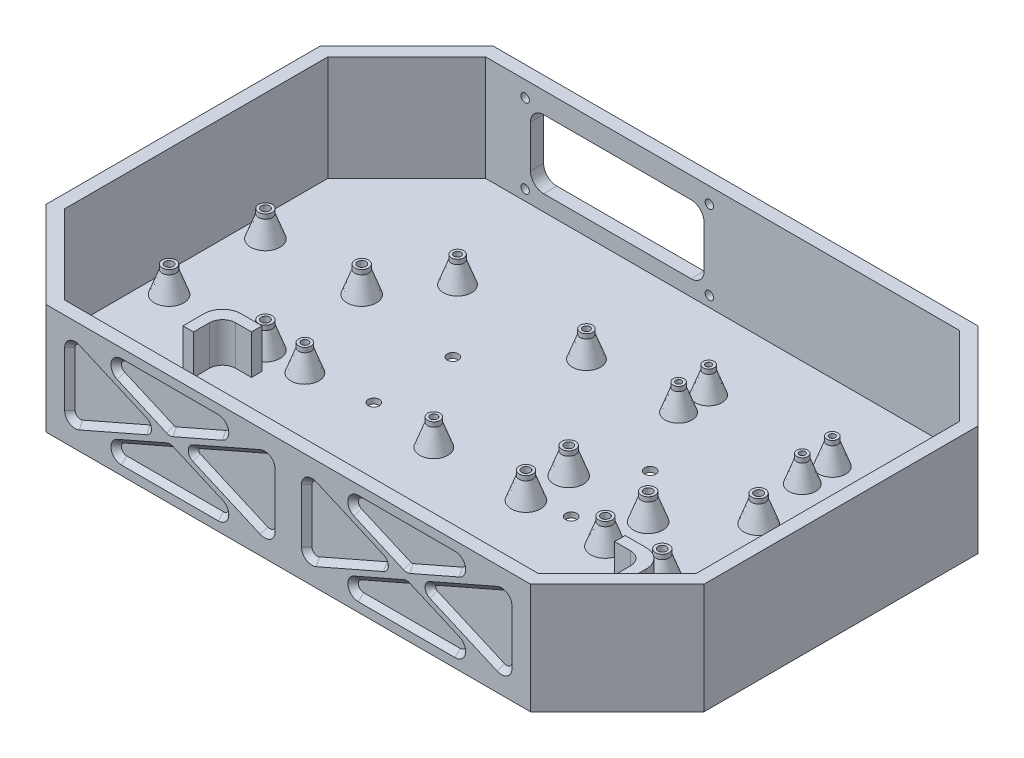
SolidWorks part; units mm, degrees
note: '?' marks a value the reader was unsure of. The reader was unsure of these and kept them because the rebuilt part matched: shared geometry of "Sketch1<3>", "Sketch2<3>", "Sketch4<3>".
ref_plane "Front Plane" through (0, 0, 0) normal (0, 0, 1) x (1, 0, 0)
ref_plane "Top Plane" through (0, 0, 0) normal (0, 1, 0) x (1, 0, 0)
ref_plane "Right Plane" through (0, 0, 0) normal (1, 0, 0) x (0, 0, -1)
ref_axis "X" through (-88.99, 0, 0) along (1, 0, 0)?
ref_axis "Y" through (0, 55, 0) along (0, -1, 0)?
ref_axis "Z" through (0, 0, -88.99) along (0, 0, 1)?
sketch "Sketch1" plane through (0, 0, 0) normal (0, 1, 0) x (1, 0, 0)
  line L0 (90, 80) -> (120, 50)
  line L1 (-90, 80) -> (90, 80)
  line L2 (-90, 80) -> (-90, -80) construction
  line L3 (-90, -80) -> (90, -80)
  line L4 (90, 80) -> (90, -80) construction
  line L5 (-90, 80) -> (90, -80) construction
  line L6 (-90, -80) -> (90, 80) construction
  line L7 (120, 50) -> (120, -50)
  line L8 (120, -50) -> (90, -80)
  line L9 (90, 0) -> (120, 0) construction
  line L10 (0, 0) -> (0, 80) construction
  line L11 (-120, -50) -> (-90, -80)
  line L12 (-120, 50) -> (-120, -50)
  line L13 (-90, 80) -> (-120, 50)
  line L14 (125, 52.0711) -> (125, -52.0711)
  line L15 (125, -52.0711) -> (92.0711, -85)
  line L16 (-92.0711, -85) -> (92.0711, -85)
  line L17 (-125, -52.0711) -> (-92.0711, -85)
  line L18 (-125, 52.0711) -> (-125, -52.0711)
  line L19 (-92.0711, 85) -> (-125, 52.0711)
  line L20 (-92.0711, 85) -> (92.0711, 85)
  line L21 (92.0711, 85) -> (125, 52.0711)
  point P0 (0, 0)
  dimension "D1" = 160
  dimension "D2" = 180
  dimension "D3" = 100
  dimension "D4" = 45
  dimension "D5" = 5
extrude "Boss-Extrude1" add sketch "Sketch1" against normal blind 2 contours L18 L17 L16 L15 L14 L21 L20 L19
extrude "Boss-Extrude2" add sketch "Sketch1<3>" along normal blind 40 contours L21 L20 L19 L18 L17 L16 L15 L14 L13 L1 L0 L7 L8 L3 L11 L12
sketch "Sketch1<3>" plane through (0, 0, 0) normal (0, 1, 0) x (1, 0, 0) same geometry as "Sketch1"
sketch "Sketch2" plane through (0, 0, 0) normal (0, 1, 0) x (1, 0, 0)
  line L0 (93.7, 0) -> (0, 0) construction
  line L1 (-112, 18.3) -> (-75.4, 18.3) construction
  line L2 (-112, 18.3) -> (-112, -18.3) construction
  line L3 (-112, -18.3) -> (-75.4, -18.3) construction
  line L4 (-75.4, 18.3) -> (-75.4, -18.3) construction
  line L5 (-112, 18.3) -> (-75.4, -18.3) construction
  line L6 (-112, -18.3) -> (-75.4, 18.3) construction
  line L7 (75.4, 18.3) -> (112, 18.3) construction
  line L8 (75.4, 18.3) -> (75.4, -18.3) construction
  line L9 (75.4, -18.3) -> (112, -18.3) construction
  line L10 (112, 18.3) -> (112, -18.3) construction
  line L11 (75.4, 18.3) -> (112, -18.3) construction
  line L12 (75.4, -18.3) -> (112, 18.3) construction
  line L13 (23.6, -2.05) -> (53.8, -2.05) construction
  line L14 (23.6, -2.05) -> (23.6, -18.3) construction
  line L15 (23.6, -18.3) -> (53.8, -18.3) construction
  line L16 (53.8, -2.05) -> (53.8, -18.3) construction
  line L17 (23.6, -2.05) -> (53.8, -18.3) construction
  line L18 (23.6, -18.3) -> (53.8, -2.05) construction
  line L19 (23.6, 51.1) -> (70.6, 51.1) construction
  line L20 (23.6, 51.1) -> (23.6, 39.7) construction
  line L21 (23.6, 39.7) -> (70.6, 39.7) construction
  line L22 (70.6, 51.1) -> (70.6, 39.7) construction
  line L23 (23.6, 51.1) -> (70.6, 39.7) construction
  line L24 (23.6, 39.7) -> (70.6, 51.1) construction
  line L25 (-60.4, 39.7) -> (-11.4, 39.7) construction
  line L26 (-60.4, 39.7) -> (-60.4, -18.3) construction
  line L27 (-60.4, -18.3) -> (-11.4, -18.3) construction
  line L28 (-11.4, 39.7) -> (-11.4, -18.3) construction
  line L29 (-60.4, 39.7) -> (-11.4, -18.3) construction
  line L30 (-60.4, -18.3) -> (-11.4, 39.7) construction
  line L31 (0, 0) -> (-93.7, 0) construction
  line L32 (120, 50) -> (120, -50) construction
  circle A0 centre (112, -18.3) radius 1.6
  circle A1 centre (75.4, -18.3) radius 1.6
  circle A2 centre (75.4, 18.3) radius 1.6
  circle A3 centre (112, 18.3) radius 1.6
  circle A4 centre (-75.4, 18.3) radius 1.6
  circle A5 centre (-75.4, -18.3) radius 1.6
  circle A6 centre (-112, -18.3) radius 1.6
  circle A7 centre (-112, 18.3) radius 1.6
  circle A8 centre (53.8, -18.3) radius 1.6
  circle A9 centre (23.6, -18.3) radius 1.6
  circle A10 centre (23.6, -2.05) radius 1.6
  circle A11 centre (53.8, -2.05) radius 1.6
  circle A12 centre (70.6, 39.7) radius 1.1
  circle A13 centre (23.6, 39.7) radius 1.1
  circle A14 centre (23.6, 51.1) radius 1.1
  circle A15 centre (70.6, 51.1) radius 1.1
  circle A16 centre (-11.4, 39.7) radius 1.35
  circle A17 centre (-60.4, 39.7) radius 1.35
  circle A18 centre (-60.4, -18.3) radius 1.35
  circle A19 centre (-11.4, -18.3) radius 1.35
  circle A20 centre (-112, 18.3) radius 2.6
  circle A21 centre (-112, -18.3) radius 2.6
  circle A22 centre (-75.4, -18.3) radius 2.6
  circle A23 centre (-75.4, 18.3) radius 2.6
  circle A24 centre (-60.4, 39.7) radius 2.35
  circle A25 centre (-11.4, 39.7) radius 2.35
  circle A26 centre (-11.4, -18.3) radius 2.35
  circle A27 centre (-60.4, -18.3) radius 2.35
  circle A28 centre (23.6, -18.3) radius 2.6
  circle A29 centre (23.6, -2.05) radius 2.6
  circle A30 centre (53.8, -2.05) radius 2.6
  circle A31 centre (53.8, -18.3) radius 2.6
  circle A32 centre (23.6, 51.1) radius 2.1
  circle A33 centre (23.6, 39.7) radius 2.1
  circle A34 centre (70.6, 39.7) radius 2.1
  circle A35 centre (70.6, 51.1) radius 2.1
  circle A36 centre (75.4, 18.3) radius 2.6
  circle A37 centre (112, 18.3) radius 2.6
  circle A38 centre (112, -18.3) radius 2.6
  circle A39 centre (75.4, -18.3) radius 2.6
  point P0 (-93.7, 0)
  point P5 (93.7, 0)
  point P10 (38.7, -10.175)
  point P16 (47.1, 45.4)
  point P21 (-35.9, 10.7)
  dimension "D9" = 3.2
  dimension "D10" = 3.2
  dimension "D11" = 2.2
  dimension "D12" = 2.7
  dimension "D1" = 36.6
  dimension "D2" = 49
  dimension "D3" = 58
  dimension "D4" = 11.4
  dimension "D5" = 47
  dimension "D6" = 16.25
  dimension "D7" = 30.2
  dimension "D8" = 35
  dimension "D13" = 8
  dimension "D14" = 15
  dimension "D15" = 1
extrude "Boss-Extrude3" add sketch "Sketch2" along normal blind 10 contours A20 | A21 | A22 | A23 | A24 | A27 | A26 | A25 | A33 | A32 | A34 | A35 | A30 | A29 | A28 | A31 | A39 | A36 | A37 | A38
extrude "Cut-Extrude1" cut sketch "Sketch2<3>" against normal through all both and the other way through all contours A6 | A7 | A4 | A5 | A18 | A17 | A19 | A16 | A13 | A14 | A15 | A12 | A2 | A11 | A10 | A9 | A8 | A1 | A3 | A0
sketch "Sketch2<3>" plane through (0, 0, 0) normal (0, 1, 0) x (1, 0, 0) same geometry as "Sketch2"
sketch "Sketch3" plane through (0, 0, 0) normal (0, 1, 0) x (1, 0, 0)
  line L0 (0, -55) -> (0, 0) construction
  line L1 (-80, -30) -> (80, -30)
  line L2 (-80, -30) -> (-80, -80)
  line L3 (-80, -80) -> (80, -80)
  line L4 (80, -30) -> (80, -80)
  line L5 (-80, -30) -> (80, -80) construction
  line L6 (-80, -80) -> (80, -30) construction
  line L8 (-80, -41) -> (-84, -41)
  line L9 (-84, -41) -> (-84, -26)
  line L10 (-84, -26) -> (-69, -26)
  line L11 (-69, -26) -> (-69, -30)
  line L12 (69, -30) -> (69, -26)
  line L13 (69, -26) -> (84, -26)
  line L14 (84, -26) -> (84, -41)
  line L15 (84, -41) -> (80, -41)
  line L16 (-90, -80) -> (90, -80) construction
  point P0 (0, -55)
  dimension "D2" = 15
  dimension "D3" = 4
  dimension "D4" = 50
  dimension "D5" = 160
extrude "Boss-Extrude4" add sketch "Sketch3" along normal blind 15 contours L11 L10 L9 L8 L2 L1 | L15 L14 L13 L12 L1 L4
fillet "Fillet1" radius 5 2 edges at (80, 7.5, 30) (-80, 7.5, 30)
fillet "Fillet2" radius 7 2 edges at (84, 7.5, 26) (-84, 7.5, 26)
sketch "Sketch4" plane through (0, 0, 0) normal (0, 0, 1) x (1, 0, 0)
  line L0 (0, -2) -> (0, 40) construction
  line L1 (-92.0711, -2) -> (92.0711, -2) construction
  line L2 (-92.0711, 40) -> (92.0711, 40) construction
  line L3 (0, 19) -> (-40, 19) construction
  line L4 (0, 19) -> (45, 19) construction
  line L5 (54.5788, 19.9162) -> (80.1984, 31.1247)
  line L6 (-75, 34) -> (-5, 34) construction
  line L7 (-75, 34) -> (-75, 4) construction
  line L8 (-75, 4) -> (-5, 4) construction
  line L9 (-5, 34) -> (-5, 4) construction
  line L10 (-75, 34) -> (-5, 4) construction
  line L11 (-75, 4) -> (-5, 34) construction
  line L12 (5, 36.5) -> (85, 36.5) construction
  line L13 (5, 36.5) -> (5, 1.5) construction
  line L14 (5, 1.5) -> (85, 1.5) construction
  line L15 (85, 36.5) -> (85, 1.5) construction
  line L16 (5, 36.5) -> (85, 1.5) construction
  line L17 (5, 1.5) -> (85, 36.5) construction
  line L18 (83, 29.2924) -> (83, 8.7076)
  line L19 (80.1984, 6.8753) -> (54.5788, 18.0838)
  line L20 (53.9796, 19) -> (45, 19) construction
  line L21 (64.1843, 30.6677) -> (45.4008, 22.4499)
  line L22 (44.5992, 22.4499) -> (25.8157, 30.6677)
  line L23 (26.6173, 34.5) -> (63.3827, 34.5)
  line L24 (45, 19) -> (45, 22.3661) construction
  line L25 (26.6173, 3.5) -> (63.3827, 3.5)
  line L26 (44.5992, 15.5501) -> (25.8157, 7.3323)
  line L27 (64.1843, 7.3323) -> (45.4008, 15.5501)
  line L28 (9.8016, 6.8753) -> (35.4212, 18.0838)
  line L29 (7, 29.2924) -> (7, 8.7076)
  line L30 (35.4212, 19.9162) -> (9.8016, 31.1247)
  line L31 (-73, 27) -> (-73, 11)
  line L32 (-68, 6) -> (-12, 6)
  line L33 (-7, 27) -> (-7, 11)
  line L34 (-68, 32) -> (-12, 32)
  line L35 (-73, 32) -> (-7, 32) construction
  line L36 (-7, 32) -> (-7, 6) construction
  line L37 (-73, 6) -> (-7, 6) construction
  line L38 (-73, 32) -> (-73, 6) construction
  arc A0 (80.1984, 31.1247) -> (83, 29.2924) centre (81, 29.2924) cw
  arc A1 (83, 8.7076) -> (80.1984, 6.8753) centre (81, 8.7076) cw
  arc A2 (54.5788, 18.0838) -> (54.5788, 19.9162) centre (54.9796, 19) cw
  arc A3 (45.4008, 22.4499) -> (44.5992, 22.4499) centre (45, 23.3661) cw
  arc A4 (25.8157, 30.6677) -> (26.6173, 34.5) centre (26.6173, 32.5) cw
  arc A5 (63.3827, 34.5) -> (64.1843, 30.6677) centre (63.3827, 32.5) cw
  arc A6 (63.3827, 3.5) -> (64.1843, 7.3323) centre (63.3827, 5.5) ccw
  arc A7 (25.8157, 7.3323) -> (26.6173, 3.5) centre (26.6173, 5.5) ccw
  arc A8 (45.4008, 15.5501) -> (44.5992, 15.5501) centre (45, 14.6339) ccw
  arc A9 (35.4212, 18.0838) -> (35.4212, 19.9162) centre (35.0204, 19) ccw
  arc A10 (7, 8.7076) -> (9.8016, 6.8753) centre (9, 8.7076) ccw
  arc A11 (9.8016, 31.1247) -> (7, 29.2924) centre (9, 29.2924) ccw
  arc A12 (-12, 32) -> (-7, 27) centre (-12, 27) cw
  arc A13 (-7, 11) -> (-12, 6) centre (-12, 11) cw
  arc A14 (-73, 11) -> (-68, 6) centre (-68, 11) ccw
  arc A15 (-73, 27) -> (-68, 32) centre (-68, 27) cw
  circle A16 centre (-75, 34) radius 1.6
  circle A17 centre (-5, 34) radius 1.6
  circle A18 centre (-5, 4) radius 1.6
  circle A19 centre (-75, 4) radius 1.6
  point P76 (-75, 3.5046)
  dimension "D4" = 3
  dimension "D5" = 1
  dimension "D6" = 2
  dimension "D8" = 3
  dimension "D13" = 5
  dimension "D14" = 3.2
  dimension "D1" = 30
  dimension "D2" = 70
  dimension "D3" = 40
  dimension "D7" = 2
  dimension "D9" = 2
  dimension "D10" = 80
  dimension "D11" = 35
  dimension "D15" = 45
  dimension "D12" = 2
extrude "Cut-Extrude2" cut sketch "Sketch4" along normal up to surface (5 mm away) from surface at -85 contours A15 L31 A14 L32 A13 L33 A12 L34 | A16 | A19 | A18 | A17 up to face at (0, 20, -80) starting at face at (0, 19, -85)
extrude "Cut-Extrude3" cut sketch "Sketch4<3>" along normal blind 2 from surface at -85 contours L30 A11 L29 A10 L28 A9 | A5 L23 A4 L22 A3 L21 | L27 A8 L26 A7 L25 A6 | A2 L19 A1 L18 A0 L5 starting at face at (0, 19, -85)
sketch "Sketch4<3>" plane through (0, 0, 0) normal (0, 0, 1) x (1, 0, 0) same geometry as "Sketch4"
sketch "Sketch5" plane through (0, 0, 0) normal (0, 0, 1) x (1, 0, 0)
  line L0 (44.5992, 15.5501) -> (25.8157, 7.3323) construction
  line L1 (64.1843, 7.3323) -> (45.4008, 15.5501) construction
  line L2 (26.6173, 3.5) -> (63.3827, 3.5) construction
  line L3 (83, 29.2924) -> (83, 8.7076) construction
  line L4 (54.5788, 19.9162) -> (80.1984, 31.1247) construction
  line L5 (80.1984, 6.8753) -> (54.5788, 18.0838) construction
  line L6 (64.1843, 30.6677) -> (45.4008, 22.4499) construction
  line L7 (26.6173, 34.5) -> (63.3827, 34.5) construction
  line L8 (44.5992, 22.4499) -> (25.8157, 30.6677) construction
  line L9 (9.8016, 6.8753) -> (35.4212, 18.0838) construction
  line L10 (7, 29.2924) -> (7, 8.7076) construction
  line L11 (35.4212, 19.9162) -> (9.8016, 31.1247) construction
  line L12 (44.5992, 15.5501) -> (25.8157, 7.3323)
  line L13 (64.1843, 7.3323) -> (45.4008, 15.5501)
  line L14 (26.6173, 3.5) -> (63.3827, 3.5)
  line L15 (83, 29.2924) -> (83, 8.7076)
  line L16 (54.5788, 19.9162) -> (80.1984, 31.1247)
  line L17 (80.1984, 6.8753) -> (54.5788, 18.0838)
  line L18 (64.1843, 30.6677) -> (45.4008, 22.4499)
  line L19 (26.6173, 34.5) -> (63.3827, 34.5)
  line L20 (44.5992, 22.4499) -> (25.8157, 30.6677)
  line L21 (9.8016, 6.8753) -> (35.4212, 18.0838)
  line L22 (7, 29.2924) -> (7, 8.7076)
  line L23 (35.4212, 19.9162) -> (9.8016, 31.1247)
  line L24 (0, -2) -> (0, 40) construction
  line L25 (0, -2) -> (0, 40) construction
  line L26 (-35.4212, 19.9162) -> (-9.8016, 31.1247)
  line L27 (-7, 29.2924) -> (-7, 8.7076)
  line L28 (-9.8016, 6.8753) -> (-35.4212, 18.0838)
  line L29 (-44.5992, 22.4499) -> (-25.8157, 30.6677)
  line L30 (-26.6173, 34.5) -> (-63.3827, 34.5)
  line L31 (-64.1843, 30.6677) -> (-45.4008, 22.4499)
  line L32 (-80.1984, 6.8753) -> (-54.5788, 18.0838)
  line L33 (-54.5788, 19.9162) -> (-80.1984, 31.1247)
  line L34 (-83, 29.2924) -> (-83, 8.7076)
  line L35 (-26.6173, 3.5) -> (-63.3827, 3.5)
  line L36 (-64.1843, 7.3323) -> (-45.4008, 15.5501)
  line L37 (-44.5992, 15.5501) -> (-25.8157, 7.3323)
  arc A0 (25.8157, 7.3323) -> (26.6173, 3.5) centre (26.6173, 5.5) ccw construction
  arc A1 (45.4008, 15.5501) -> (44.5992, 15.5501) centre (45, 14.6339) ccw construction
  arc A2 (63.3827, 3.5) -> (64.1843, 7.3323) centre (63.3827, 5.5) ccw construction
  arc A3 (80.1984, 6.8753) -> (83, 8.7076) centre (81, 8.7076) ccw construction
  arc A4 (83, 29.2924) -> (80.1984, 31.1247) centre (81, 29.2924) ccw construction
  arc A5 (54.5788, 19.9162) -> (54.5788, 18.0838) centre (54.9796, 19) ccw construction
  arc A6 (44.5992, 22.4499) -> (45.4008, 22.4499) centre (45, 23.3661) ccw construction
  arc A7 (64.1843, 30.6677) -> (63.3827, 34.5) centre (63.3827, 32.5) ccw construction
  arc A8 (26.6173, 34.5) -> (25.8157, 30.6677) centre (26.6173, 32.5) ccw construction
  arc A9 (35.4212, 18.0838) -> (35.4212, 19.9162) centre (35.0204, 19) ccw construction
  arc A10 (7, 8.7076) -> (9.8016, 6.8753) centre (9, 8.7076) ccw construction
  arc A11 (9.8016, 31.1247) -> (7, 29.2924) centre (9, 29.2924) ccw construction
  arc A12 (25.8157, 7.3323) -> (26.6173, 3.5) centre (26.6173, 5.5) ccw
  arc A13 (45.4008, 15.5501) -> (44.5992, 15.5501) centre (45, 14.6339) ccw
  arc A14 (63.3827, 3.5) -> (64.1843, 7.3323) centre (63.3827, 5.5) ccw
  arc A15 (80.1984, 6.8753) -> (83, 8.7076) centre (81, 8.7076) ccw
  arc A16 (83, 29.2924) -> (80.1984, 31.1247) centre (81, 29.2924) ccw
  arc A17 (54.5788, 19.9162) -> (54.5788, 18.0838) centre (54.9796, 19) ccw
  arc A18 (44.5992, 22.4499) -> (45.4008, 22.4499) centre (45, 23.3661) ccw
  arc A19 (64.1843, 30.6677) -> (63.3827, 34.5) centre (63.3827, 32.5) ccw
  arc A20 (26.6173, 34.5) -> (25.8157, 30.6677) centre (26.6173, 32.5) ccw
  arc A21 (35.4212, 18.0838) -> (35.4212, 19.9162) centre (35.0204, 19) ccw
  arc A22 (7, 8.7076) -> (9.8016, 6.8753) centre (9, 8.7076) ccw
  arc A23 (9.8016, 31.1247) -> (7, 29.2924) centre (9, 29.2924) ccw
  arc A24 (-9.8016, 31.1247) -> (-7, 29.2924) centre (-9, 29.2924) cw
  arc A25 (-7, 8.7076) -> (-9.8016, 6.8753) centre (-9, 8.7076) cw
  arc A26 (-35.4212, 18.0838) -> (-35.4212, 19.9162) centre (-35.0204, 19) cw
  arc A27 (-26.6173, 34.5) -> (-25.8157, 30.6677) centre (-26.6173, 32.5) cw
  arc A28 (-64.1843, 30.6677) -> (-63.3827, 34.5) centre (-63.3827, 32.5) cw
  arc A29 (-44.5992, 22.4499) -> (-45.4008, 22.4499) centre (-45, 23.3661) cw
  arc A30 (-54.5788, 19.9162) -> (-54.5788, 18.0838) centre (-54.9796, 19) cw
  arc A31 (-83, 29.2924) -> (-80.1984, 31.1247) centre (-81, 29.2924) cw
  arc A32 (-80.1984, 6.8753) -> (-83, 8.7076) centre (-81, 8.7076) cw
  arc A33 (-63.3827, 3.5) -> (-64.1843, 7.3323) centre (-63.3827, 5.5) cw
  arc A34 (-45.4008, 15.5501) -> (-44.5992, 15.5501) centre (-45, 14.6339) cw
  arc A35 (-25.8157, 7.3323) -> (-26.6173, 3.5) centre (-26.6173, 5.5) cw
extrude "Cut-Extrude4" cut sketch "Sketch5" against normal blind 2 from surface at 85 starting at face at (0, 19, 85)
chamfer "Chamfer1" distance 2 angle 45 72 edges at (45, 15.6339, -85) (35.2074, 11.4412, -85) (54.7926, 11.4412, -85) (24.6597, 5.0905, -85) (65.3403, 5.0905, -85) (45, 3.5, -85) (45, 22.3661, -85) (35.2074, 26.5588, -85) (54.7926, 26.5588, -85) (24.6597, 32.9095, -85) (65.3403, 32.9095, -85) (45, 34.5, -85) (53.9796, 19, -85) (67.3886, 25.5204, -85) (67.3886, 12.4796, -85) (82.0947, 30.9662, -85) (82.0947, 7.0338, -85) (83, 19, -85) (36.0204, 19, -85) (22.6114, 25.5204, -85) (22.6114, 12.4796, -85) (7.9053, 30.9662, -85) (7.9053, 7.0338, -85) (7, 19, -85) (53.9796, 19, 85) (67.3886, 25.5204, 85) (67.3886, 12.4796, 85) (82.0947, 30.9662, 85) (82.0947, 7.0338, 85) (83, 19, 85) (45, 22.3661, 85) (35.2074, 26.5588, 85) (54.7926, 26.5588, 85) (24.6597, 32.9095, 85) (65.3403, 32.9095, 85) (45, 34.5, 85) (45, 15.6339, 85) (54.7926, 11.4412, 85) (35.2074, 11.4412, 85) (65.3403, 5.0905, 85) (24.6597, 5.0905, 85) (45, 3.5, 85) (36.0204, 19, 85) (22.6114, 12.4796, 85) (22.6114, 25.5204, 85) (7.9053, 7.0338, 85) (7.9053, 30.9662, 85) (7, 19, 85) (-36.0204, 19, 85) (-22.6114, 25.5204, 85) (-22.6114, 12.4796, 85) (-7.9053, 30.9662, 85) (-7.9053, 7.0338, 85) (-7, 19, 85) (-45, 15.6339, 85) (-35.2074, 11.4412, 85) (-54.7926, 11.4412, 85) (-24.6597, 5.0905, 85) (-65.3403, 5.0905, 85) (-45, 3.5, 85) (-45, 22.3661, 85) (-54.7926, 26.5588, 85) (-35.2074, 26.5588, 85) (-65.3403, 32.9095, 85) (-24.6597, 32.9095, 85) (-45, 34.5, 85) (-53.9796, 19, 85) (-67.3886, 12.4796, 85) (-67.3886, 25.5204, 85) (-82.0947, 7.0338, 85) (-82.0947, 30.9662, 85) (-83, 19, 85)
sketch "Sketch6" plane through (0, 0, 0) normal (0, 1, 0) x (1, 0, 0)
  line L1 (-37.5, 15) -> (37.5, 15) construction
  line L2 (-37.5, 15) -> (-37.5, -15) construction
  line L3 (-37.5, -15) -> (37.5, -15) construction
  line L4 (37.5, 15) -> (37.5, -15) construction
  line L5 (-37.5, 15) -> (37.5, -15) construction
  line L6 (-37.5, -15) -> (37.5, 15) construction
  circle A0 centre (37.5, 15) radius 2.1
  circle A1 centre (37.5, -15) radius 2.1
  circle A2 centre (-37.5, -15) radius 2.1
  circle A3 centre (-37.5, 15) radius 2.1
  point P0 (0, 0)
  dimension "D3" = 4.2
  dimension "D1" = 30
  dimension "D2" = 75
extrude "Cut-Extrude5" cut sketch "Sketch6" against normal through all both and the other way through all
chamfer "Chamfer2" distance 3 angle 70 20 edges at (-75.4, 0, 20.9) (112, 0, 20.9) (75.4, 0, 20.9) (112, 0, -15.7) (75.4, 0, -15.7) (70.6, 0, -49) (70.6, 0, -37.6) (53.8, 0, 4.65) (53.8, 0, 20.9) (23.6, 0, 20.9) (23.6, 0, 4.65) (23.6, 0, -37.6) (23.6, 0, -49) (-11.4, 0, -37.35) (-11.4, 0, 20.65) (-60.4, 0, 20.65) (-60.4, 0, -37.35) (-75.4, 0, -15.7) (-112, 0, 20.9) (-112, 0, -15.7) first distance on face at (-37.5, 0, -12.9)
